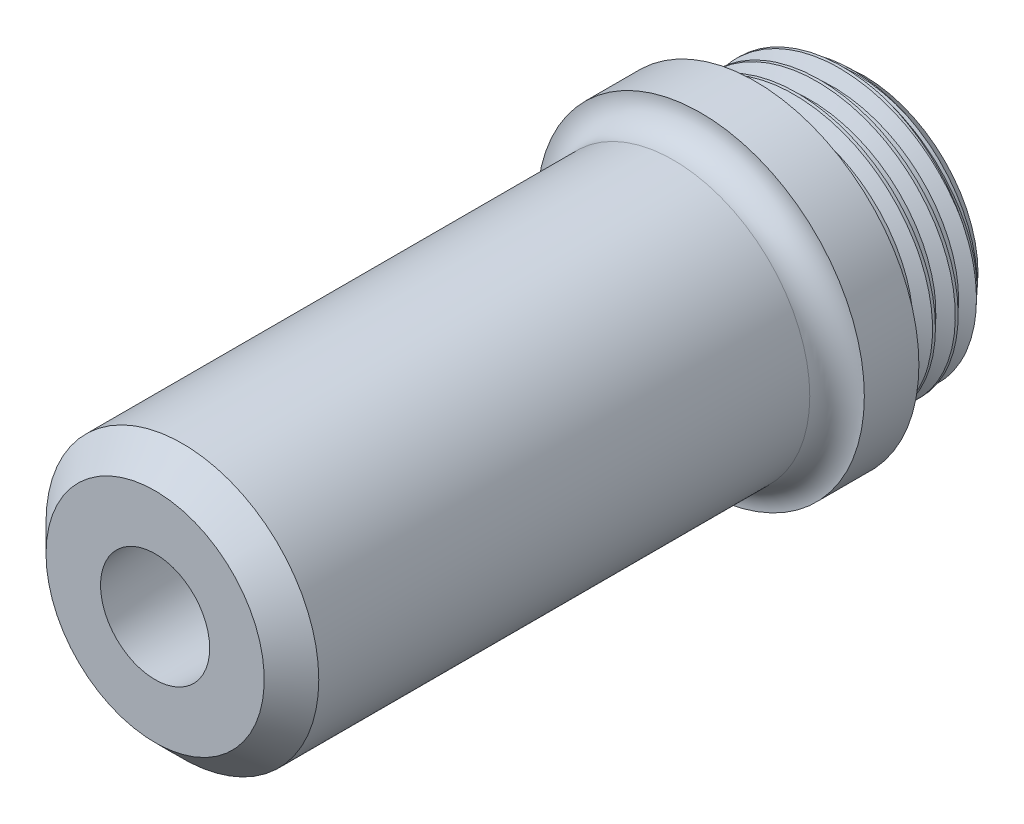
SolidWorks part; units mm, degrees
material "Plain Carbon Steel"
ref_plane "Front Plane" through (0, 0, 0) normal (0, 0, 1) x (1, 0, 0)
ref_plane "Top Plane" through (0, 0, 0) normal (0, 1, 0) x (1, 0, 0)
ref_plane "Right Plane" through (0, 0, 0) normal (1, 0, 0) x (0, 0, -1)
sketch "Sketch1" plane through (0, 0, 0) normal (0, 0, 1) x (1, 0, 0)
  circle A0 centre (0, 0) radius 7.62
  dimension "D1" = 15.24
extrude "Boss-Extrude1" add sketch "Sketch1" along normal blind 2.54
sketch "Sketch2" plane through (0, 0, 0) normal (0, 0, -1) x (-1, 0, 0)
  circle A0 centre (0, 0) radius 6.35
  dimension "D1" = 12.7
extrude "Boss-Extrude2" add sketch "Sketch2" along normal blind 5.08 and the other way blind 27.94
thread "Thread1" pitch 1.0583 method cut profile "Thread Profile1" start angle 0, offset 0, length 5.461, pitch 1.0583, diameter 12.7
ref_plane "Plane1" through (6.35, 0, -5.08) normal (0, -1, 0) x (1, 0, 0)
sketch "Thread Profile1" plane through (6.35, 0, -5.08) normal (0, -1, 0) x (1, 0, 0)
  line L0 (0, 0) -> (0, 1.0583) construction
  line L11 (0, 0) -> (0, 0.926)
  line L12 (0, 0.926) -> (-0.5728, 0.5953)
  line L13 (-0.5728, 0.5953) -> (-0.5728, 0.3307)
  line L15 (-0.5728, 0.3307) -> (0, 0)
  line L17 (-0.5728, 0.463) -> (0, 0.463) construction
  point P2 (0, 0)
  dimension "Pitch" = 1.0583
  dimension "Profile_Angle" = 60
  dimension "Profile_Land" = 0.2646
  dimension "Profile_Height" = 0.5728
sketch "Sketch6" plane through (0, 0, 0) normal (0, 1, 0) x (1, 0, 0)
  line L0 (0, 0) -> (0, 5.08) construction
  line L1 (6.35, 5.08) -> (-6.35, 5.08) construction
  line L2 (4.699, 5.715) -> (6.477, 3.81)
  line L3 (6.477, 3.81) -> (6.477, 5.715)
  line L4 (6.477, 5.715) -> (4.699, 5.715)
  dimension "D1" = 4.699
  dimension "D2" = 1.778
  dimension "D3" = 1.905
  dimension "D4" = 0.635
revolve "Cut-Revolve1" cut sketch "Sketch6" angle 360 about L0
fillet "Fillet1" radius 1.27 1 edges at (6.35, 0, 2.54)
chamfer "Chamfer1" distance 1.27 angle 45 1 edges at (-6.35, 0, 27.94)
sketch "Sketch7" plane through (0, 0, 27.94) normal (0, 0, 1) x (1, 0, 0)
  circle A0 centre (0, 0) radius 2.54
  dimension "D1" = 5.08
extrude "Cut-Extrude1" cut sketch "Sketch7" against normal through all draft 4 draft outward yes
